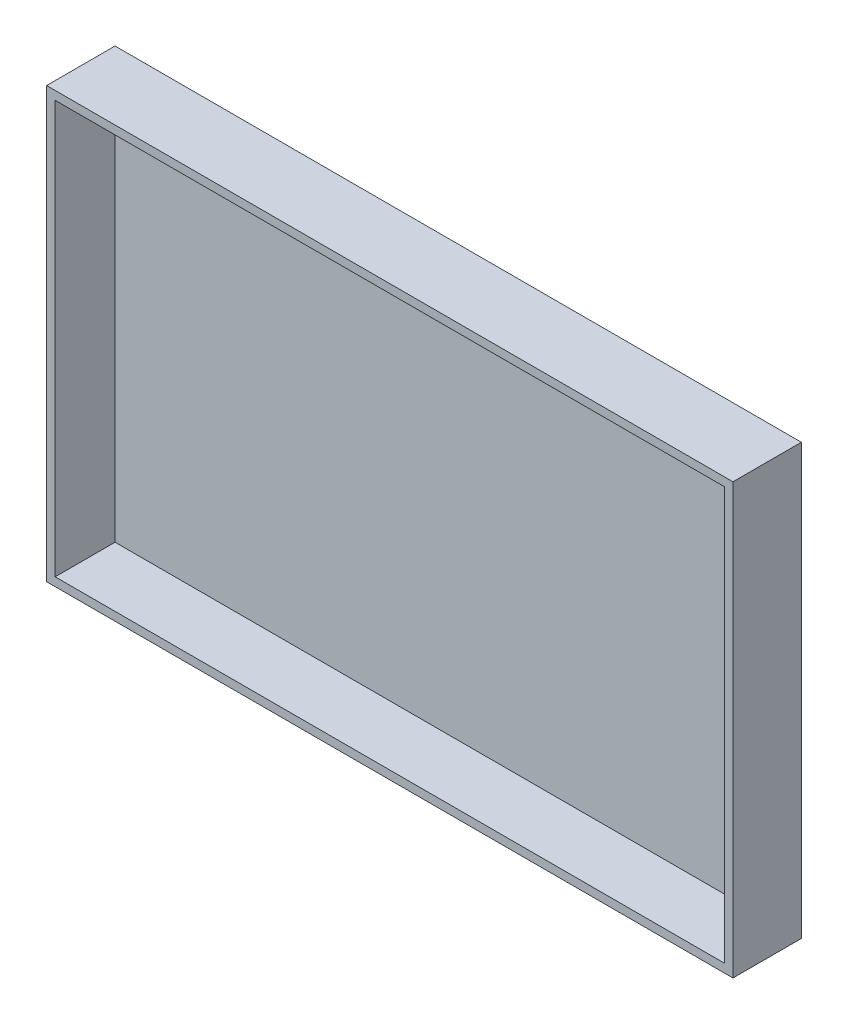
SolidWorks part; units mm, degrees
ref_plane "Plan de face" through (0, 0, 0) normal (0, 0, 1) x (1, 0, 0)
ref_plane "Plan de dessus" through (0, 0, 0) normal (0, 1, 0) x (1, 0, 0)
ref_plane "Plan de droite" through (0, 0, 0) normal (1, 0, 0) x (0, 0, -1)
sketch "Esquisse1" plane through (0, 0, 0) normal (0, 0, 1) x (1, 0, 0)
  line L1 (-51.1381, 30.218) -> (109.3619, 30.218)
  line L2 (-51.1381, 30.218) -> (-51.1381, -70.282)
  line L3 (-51.1381, -70.282) -> (109.3619, -70.282)
  line L4 (109.3619, 30.218) -> (109.3619, -70.282)
  dimension "D1" = 160.5
  dimension "D2" = 100.5
extrude "Boss.-Extru.1" add sketch "Esquisse1" along normal blind 2
sketch "Esquisse2" plane through (0, 0, 2) normal (0, 0, 1) x (1, 0, 0)
  line L1 (-51.1381, 30.218) -> (109.3619, 30.218)
  line L2 (-51.1381, 30.218) -> (-51.1381, -70.282)
  line L3 (-51.1381, -70.282) -> (109.3619, -70.282)
  line L4 (109.3619, 30.218) -> (109.3619, -70.282)
  line L5 (-49.1381, 28.218) -> (107.3619, 28.218)
  line L6 (-49.1381, 28.218) -> (-49.1381, -68.282)
  line L7 (-49.1381, -68.282) -> (107.3619, -68.282)
  line L8 (107.3619, 28.218) -> (107.3619, -68.282)
  dimension "D1" = 2
  dimension "D2" = 2
  dimension "D3" = 2
  dimension "D4" = 2
extrude "Boss.-Extru.2" add sketch "Esquisse2" along normal blind 14
